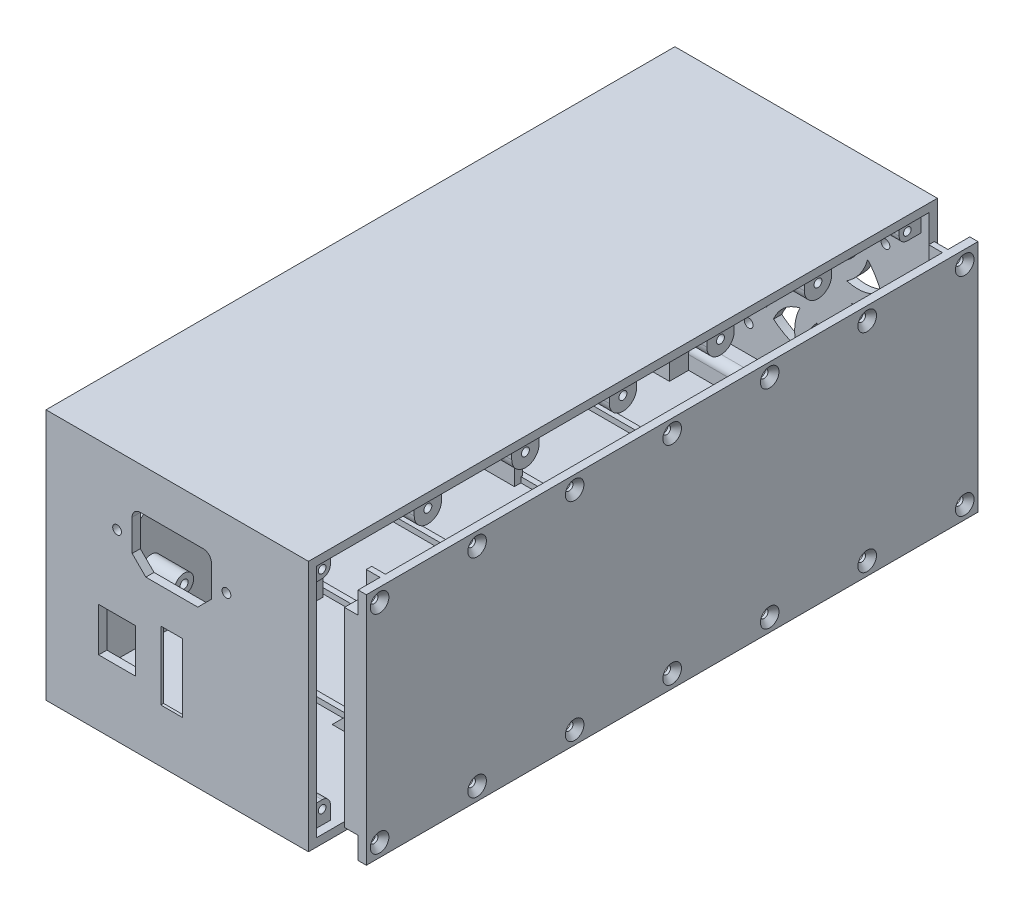
SolidWorks part; units mm, degrees
ref_plane "Front Plane" through (0, 0, 0) normal (0, 0, 1) x (1, 0, 0)
ref_plane "Top Plane" through (0, 0, 0) normal (0, 1, 0) x (1, 0, 0)
ref_plane "Right Plane" through (0, 0, 0) normal (1, 0, 0) x (0, 0, -1)
sketch "Sketch1" plane through (0, 0, 0) normal (1, 0, 0) x (0, 0, -1)
  line L1 (115, 46) -> (-115, 46)
  line L2 (115, 46) -> (115, -46)
  line L3 (115, -46) -> (-115, -46)
  line L4 (-115, 46) -> (-115, -46)
  line L5 (115, 46) -> (-115, -46) construction
  line L6 (115, -46) -> (-115, 46) construction
  point P0 (0, 0)
  dimension "D1" = 92
  dimension "D2" = 230
extrude "Boss-Extrude1" add sketch "Sketch1" along normal blind 3
sketch "Sketch2" plane through (3, 0, 0) normal (1, 0, 0) x (0, 0, -1)
  line L0 (-112, 43) -> (-112, -43)
  line L1 (-112, -43) -> (112, -43)
  line L2 (112, -43) -> (112, 43)
  line L3 (112, 43) -> (-112, 43)
  line L4 (-115, 46) -> (-115, -46)
  line L5 (-115, -46) -> (115, -46)
  line L6 (115, -46) -> (115, 46)
  line L7 (115, 46) -> (-115, 46)
  line L8 (-115, 46) -> (-115, -46)
  line L9 (-115, -46) -> (115, -46)
  line L10 (115, -46) -> (115, 46)
  line L11 (115, 46) -> (-115, 46)
  dimension "D1" = 0
  dimension "D2" = 3
extrude "Boss-Extrude2" add sketch "Sketch2" along normal blind 93
sketch "Sketch3" plane through (0, 0, 0) normal (-1, 0, 0) x (0, 0, 1)
  line L0 (-115, 0) -> (115, 0) construction
  line L1 (-115, -46) -> (-115, 46) construction
  line L2 (115, 46) -> (115, -46) construction
  line L3 (0, 46) -> (0, -46) construction
  line L4 (-115, 46) -> (115, 46) construction
  line L5 (115, -46) -> (-115, -46) construction
  line L6 (26.5, -7.75) -> (18.5, -7.75)
  line L7 (11.5, 7.75) -> (3.5, 7.75)
  line L8 (11.5, 7.75) -> (11.5, -7.75)
  line L9 (11.5, -7.75) -> (3.5, -7.75)
  line L10 (3.5, 7.75) -> (3.5, -7.75)
  line L11 (11.5, 7.75) -> (3.5, -7.75) construction
  line L12 (11.5, -7.75) -> (3.5, 7.75) construction
  line L13 (26.5, 7.75) -> (26.5, -7.75)
  line L14 (26.5, 7.75) -> (18.5, 7.75)
  line L15 (18.5, 7.75) -> (18.5, -7.75)
  line L16 (41.5, -7.75) -> (33.5, -7.75)
  line L17 (41.5, 7.75) -> (41.5, -7.75)
  line L18 (41.5, 7.75) -> (33.5, 7.75)
  line L19 (33.5, 7.75) -> (33.5, -7.75)
  line L20 (56.5, -7.75) -> (48.5, -7.75)
  line L21 (56.5, 7.75) -> (56.5, -7.75)
  line L22 (56.5, 7.75) -> (48.5, 7.75)
  line L23 (48.5, 7.75) -> (48.5, -7.75)
  line L24 (71.5, -7.75) -> (63.5, -7.75)
  line L25 (71.5, 7.75) -> (71.5, -7.75)
  line L26 (71.5, 7.75) -> (63.5, 7.75)
  line L27 (63.5, 7.75) -> (63.5, -7.75)
  line L28 (11.5, -7.75) -> (3.5, -7.75)
  line L29 (11.5, 7.75) -> (11.5, -7.75)
  line L30 (11.5, 7.75) -> (3.5, 7.75)
  line L31 (3.5, 7.75) -> (3.5, -7.75)
  line L32 (26.5, -7.75) -> (18.5, -7.75)
  line L33 (26.5, 7.75) -> (26.5, -7.75)
  line L34 (26.5, 7.75) -> (18.5, 7.75)
  line L35 (18.5, 7.75) -> (18.5, -7.75)
  line L36 (41.5, -7.75) -> (33.5, -7.75)
  line L37 (41.5, 7.75) -> (41.5, -7.75)
  line L38 (41.5, 7.75) -> (33.5, 7.75)
  line L39 (33.5, 7.75) -> (33.5, -7.75)
  line L40 (56.5, -7.75) -> (48.5, -7.75)
  line L41 (56.5, 7.75) -> (56.5, -7.75)
  line L42 (56.5, 7.75) -> (48.5, 7.75)
  line L43 (48.5, 7.75) -> (48.5, -7.75)
  line L44 (-3.5, -7.75) -> (-11.5, -7.75)
  line L45 (-3.5, 7.75) -> (-3.5, -7.75)
  line L46 (-3.5, 7.75) -> (-11.5, 7.75)
  line L47 (-11.5, 7.75) -> (-11.5, -7.75)
  line L48 (11.5, -7.75) -> (3.5, -7.75)
  line L49 (11.5, 7.75) -> (11.5, -7.75)
  line L50 (11.5, 7.75) -> (3.5, 7.75)
  line L51 (3.5, 7.75) -> (3.5, -7.75)
  line L52 (26.5, -7.75) -> (18.5, -7.75)
  line L53 (26.5, 7.75) -> (26.5, -7.75)
  line L54 (26.5, 7.75) -> (18.5, 7.75)
  line L55 (18.5, 7.75) -> (18.5, -7.75)
  line L56 (41.5, -7.75) -> (33.5, -7.75)
  line L57 (41.5, 7.75) -> (41.5, -7.75)
  line L58 (41.5, 7.75) -> (33.5, 7.75)
  line L59 (33.5, 7.75) -> (33.5, -7.75)
  line L60 (-18.5, -7.75) -> (-26.5, -7.75)
  line L61 (-18.5, 7.75) -> (-18.5, -7.75)
  line L62 (-18.5, 7.75) -> (-26.5, 7.75)
  line L63 (-26.5, 7.75) -> (-26.5, -7.75)
  line L64 (-3.5, -7.75) -> (-11.5, -7.75)
  line L65 (-3.5, 7.75) -> (-3.5, -7.75)
  line L66 (-3.5, 7.75) -> (-11.5, 7.75)
  line L67 (-11.5, 7.75) -> (-11.5, -7.75)
  line L68 (11.5, -7.75) -> (3.5, -7.75)
  line L69 (11.5, 7.75) -> (11.5, -7.75)
  line L70 (11.5, 7.75) -> (3.5, 7.75)
  line L71 (3.5, 7.75) -> (3.5, -7.75)
  line L72 (26.5, -7.75) -> (18.5, -7.75)
  line L73 (26.5, 7.75) -> (26.5, -7.75)
  line L74 (26.5, 7.75) -> (18.5, 7.75)
  line L75 (18.5, 7.75) -> (18.5, -7.75)
  line L76 (-33.5, -7.75) -> (-41.5, -7.75)
  line L77 (-33.5, 7.75) -> (-33.5, -7.75)
  line L78 (-33.5, 7.75) -> (-41.5, 7.75)
  line L79 (-41.5, 7.75) -> (-41.5, -7.75)
  line L80 (-18.5, -7.75) -> (-26.5, -7.75)
  line L81 (-18.5, 7.75) -> (-18.5, -7.75)
  line L82 (-18.5, 7.75) -> (-26.5, 7.75)
  line L83 (-26.5, 7.75) -> (-26.5, -7.75)
  line L84 (-3.5, -7.75) -> (-11.5, -7.75)
  line L85 (-3.5, 7.75) -> (-3.5, -7.75)
  line L86 (-3.5, 7.75) -> (-11.5, 7.75)
  line L87 (-11.5, 7.75) -> (-11.5, -7.75)
  line L88 (11.5, -7.75) -> (3.5, -7.75)
  line L89 (11.5, 7.75) -> (11.5, -7.75)
  line L90 (11.5, 7.75) -> (3.5, 7.75)
  line L91 (3.5, 7.75) -> (3.5, -7.75)
  line L92 (-48.5, -7.75) -> (-56.5, -7.75)
  line L93 (-48.5, 7.75) -> (-48.5, -7.75)
  line L94 (-48.5, 7.75) -> (-56.5, 7.75)
  line L95 (-56.5, 7.75) -> (-56.5, -7.75)
  line L96 (-33.5, -7.75) -> (-41.5, -7.75)
  line L97 (-33.5, 7.75) -> (-33.5, -7.75)
  line L98 (-33.5, 7.75) -> (-41.5, 7.75)
  line L99 (-41.5, 7.75) -> (-41.5, -7.75)
  line L100 (-18.5, -7.75) -> (-26.5, -7.75)
  line L101 (-18.5, 7.75) -> (-18.5, -7.75)
  line L102 (-18.5, 7.75) -> (-26.5, 7.75)
  line L103 (-26.5, 7.75) -> (-26.5, -7.75)
  line L104 (-3.5, -7.75) -> (-11.5, -7.75)
  line L105 (-3.5, 7.75) -> (-3.5, -7.75)
  line L106 (-3.5, 7.75) -> (-11.5, 7.75)
  line L107 (-11.5, 7.75) -> (-11.5, -7.75)
  line L108 (-3.5, -7.75) -> (-11.5, -7.75)
  line L109 (-3.5, 7.75) -> (-3.5, -7.75)
  line L110 (-3.5, 7.75) -> (-11.5, 7.75)
  line L111 (-11.5, 7.75) -> (-11.5, -7.75)
  line L112 (-18.5, -7.75) -> (-26.5, -7.75)
  line L113 (-18.5, 7.75) -> (-18.5, -7.75)
  line L114 (-18.5, 7.75) -> (-26.5, 7.75)
  line L115 (-26.5, 7.75) -> (-26.5, -7.75)
  line L116 (-33.5, -7.75) -> (-41.5, -7.75)
  line L117 (-33.5, 7.75) -> (-33.5, -7.75)
  line L118 (-33.5, 7.75) -> (-41.5, 7.75)
  line L119 (-41.5, 7.75) -> (-41.5, -7.75)
  line L120 (-48.5, -7.75) -> (-56.5, -7.75)
  line L121 (-48.5, 7.75) -> (-48.5, -7.75)
  line L122 (-48.5, 7.75) -> (-56.5, 7.75)
  line L123 (-56.5, 7.75) -> (-56.5, -7.75)
  line L124 (-63.5, -7.75) -> (-71.5, -7.75)
  line L125 (-63.5, 7.75) -> (-63.5, -7.75)
  line L126 (-63.5, 7.75) -> (-71.5, 7.75)
  line L127 (-71.5, 7.75) -> (-71.5, -7.75)
  circle A0 centre (84.6037, 0) radius 1
  point P12 (7.5, 0)
  dimension "D6" = 2
  dimension "D1" = 7.5
  dimension "D2" = 15.5
  dimension "D3" = 8
  dimension "D4" = 5
  dimension "D5" = 6
extrude "Cut-Extrude1" cut sketch "Sketch3" against normal up to surface (3 mm away) contours L126 L127 L124 L125 | L94 L95 L92 L93 | L78 L79 L76 L77 | L62 L63 L60 L61 | L46 L47 L44 L45 | L7 L10 L9 L8 | L14 L15 L6 L13 | L18 L19 L16 L17 | L22 L23 L20 L21 | L26 L27 L24 L25 | A0 region at (0, 0, 22.5) region at (0, 0, 7.5) region at (0, 0, 37.5) region at (0, 0, 52.5) region at (0, 0, 67.5) region at (0, 0, -7.5) region at (0, 0, -22.5) region at (0, 0, -37.5) region at (0, 0, -52.5) region at (0, 0, -67.5) region at (0, 0, 84.6037) up to face at (3, 0, 0)
sketch "Sketch4" plane through (96, 0, 0) normal (1, 0, 0) x (0, 0, -1)
  line L0 (0, 43) -> (0, -43) construction
  line L1 (112, 43) -> (-112, 43) construction
  line L2 (-112, -43) -> (112, -43) construction
  line L3 (-112, 43) -> (-112, -43) construction
  line L4 (-104, 38) -> (-104, 43)
  line L5 (-104, 43) -> (-112, 43)
  line L6 (-112, 43) -> (-112, 35)
  line L7 (-112, 35) -> (-107, 35)
  line L8 (0, 0) -> (-112, 0) construction
  line L9 (-107, -35) -> (-112, -35)
  line L10 (-112, 43) -> (-112, -43) construction
  line L11 (-112, -35) -> (-112, -43)
  line L12 (-104, -38) -> (-104, -43)
  line L13 (-104, -43) -> (-112, -43)
  line L14 (104, -43) -> (112, -43)
  line L15 (112, -35) -> (112, -43)
  line L16 (107, -35) -> (112, -35)
  line L17 (112, 35) -> (107, 35)
  line L18 (112, 43) -> (112, 35)
  line L19 (104, 43) -> (112, 43)
  line L20 (104, 38) -> (104, 43)
  line L21 (104, -38) -> (104, -43)
  circle A0 centre (-107, 38) radius 1.4
  circle A1 centre (-107, -38) radius 1.4
  arc A2 (-104, 38) -> (-107, 35) centre (-107, 38) cw
  arc A3 (-107, -35) -> (-104, -38) centre (-107, -38) cw
  arc A4 (107, -35) -> (104, -38) centre (107, -38) ccw
  circle A5 centre (107, -38) radius 1.4
  arc A6 (104, 38) -> (107, 35) centre (107, 38) ccw
  circle A7 centre (107, 38) radius 1.4
  dimension "D5" = 2.8
  dimension "D6" = 3
  dimension "D1" = 5
  dimension "D2" = 5
  dimension "D3" = 5
  dimension "D4" = 5
extrude "Boss-Extrude3" add sketch "Sketch4" against normal up to surface (93 mm away) from offset 3 up to face at (3, 0, -67.5) offset against normal yes
sketch "Sketch5" plane through (93, 0, 0) normal (1, 0, 0) x (0, 0, -1)
  circle A0 centre (-107, -38) radius 1.4 construction
  circle A1 centre (107, -38) radius 1.4 construction
  circle A2 centre (107, 38) radius 1.4 construction
  circle A3 centre (-107, 38) radius 1.4 construction
  circle A4 centre (-107, -38) radius 1.4
  circle A5 centre (107, -38) radius 1.4
  circle A6 centre (107, 38) radius 1.4
  circle A7 centre (-107, 38) radius 1.4
extrude "Boss-Extrude4" add sketch "Sketch5" against normal up to surface (90 mm away) from offset 20 up to face at (3, 0, -67.5) offset against normal yes
sketch "Sketch6" plane through (0, 0, 115) normal (0, 0, 1) x (1, 0, 0)
  line L0 (46, 46) -> (46, -46) construction
  line L1 (96, 46) -> (0, 46) construction
  line L2 (96, -46) -> (0, -46) construction
  line L3 (93, 43) -> (93, 38) construction
  line L4 (79.2275, 21) -> (12.7725, 21) construction
  line L5 (36.5, 11.25) -> (31.5, 16.25)
  line L6 (57.5, 30.75) -> (34.5, 30.75)
  line L7 (60.5, 27.75) -> (60.5, 16.25)
  line L8 (55.5, 11.25) -> (36.5, 11.25)
  line L9 (31.5, 27.75) -> (31.5, 16.25)
  line L10 (60.5, 30.75) -> (31.5, 11.25) construction
  line L11 (60.5, 11.25) -> (31.5, 30.75) construction
  line L12 (60.5, 16.25) -> (55.5, 11.25)
  line L14 (50, -1.5) -> (42, -1.5)
  line L15 (50, -1.5) -> (50, -26.5)
  line L16 (50, -26.5) -> (42, -26.5)
  line L17 (42, -1.5) -> (42, -26.5)
  line L18 (50, -1.5) -> (42, -26.5) construction
  line L19 (50, -26.5) -> (42, -1.5) construction
  line L20 (32.75, -6) -> (19.25, -6)
  line L21 (32.75, -6) -> (32.75, -22)
  line L22 (32.75, -22) -> (19.25, -22)
  line L23 (19.25, -6) -> (19.25, -22)
  line L24 (32.75, -6) -> (19.25, -22) construction
  line L25 (32.75, -22) -> (19.25, -6) construction
  circle A2 centre (26, 21) radius 1.6
  circle A3 centre (66, 21) radius 1.6
  arc A4 (57.5, 30.75) -> (60.5, 27.75) centre (57.5, 27.75) cw
  arc A5 (34.5, 30.75) -> (31.5, 27.75) centre (34.5, 27.75) ccw
  point P11 (46, 21)
  point P15 (46, 21)
  point P30 (46, -14)
  point P35 (26, -14)
  dimension "D2" = 3.2
  dimension "D7" = 3
  dimension "D1" = 47
  dimension "D3" = 20
  dimension "D4" = 20
  dimension "D5" = 29
  dimension "D6" = 19.5
  dimension "D8" = 25
  dimension "D9" = 8
  dimension "D10" = 25
  dimension "D13" = 32
  dimension "D14" = 20
  dimension "D15" = 13.5
  dimension "D16" = 16
extrude "Cut-Extrude2" cut sketch "Sketch6" against normal up to surface (3 mm away) up to face at (71.25, 0, 112)
sketch "Sketch7" plane through (0, 0, 112) normal (0, 0, -1) x (-1, 0, 0)
  line L0 (-39.5, 6) -> (-39.5, -32.5)
  line L1 (-39.5, -32.5) -> (-52, -32.5)
  line L2 (-52, -32.5) -> (-52, 6)
  line L3 (-52, 6) -> (-39.5, 6)
  line L4 (-50, -1.5) -> (-42, -1.5) construction
  line L5 (-50, -26.5) -> (-50, -1.5) construction
  dimension "D1" = 7.5
  dimension "D2" = 2
  dimension "D3" = 38.5
  dimension "D4" = 12.5
extrude "Cut-Extrude3" cut sketch "Sketch7" against normal blind 2
chamfer "Chamfer1" distance 2 angle 45 1 edges at (52, -13.25, 112)
sketch "Sketch8" plane through (3, 0, 0) normal (1, 0, 0) x (0, 0, -1)
  line L0 (-71.5, 0) -> (91.1958, 0) construction
  line L1 (-71.5, -7.75) -> (-71.5, 7.75) construction
  line L2 (-79.5, 43) -> (-79.5, -43) construction
  line L3 (112, 43) -> (-112, 43) construction
  line L4 (-104, -43) -> (104, -43) construction
  circle A0 centre (-79.5, 19.5) radius 1.5
  circle A1 centre (-79.5, -19.5) radius 1.5
  circle A2 centre (-79.5, 19.5) radius 3.5
  circle A3 centre (-79.5, -19.5) radius 3.5
  circle A4 centre (72, -19.5) radius 1.5
  circle A5 centre (72, -19.5) radius 3.5
  circle A6 centre (72, 19.5) radius 3.5
  circle A7 centre (72, 19.5) radius 1.5
  dimension "D1" = 3
  dimension "D2" = 7
  dimension "D3" = 8
  dimension "D5" = 19.5
  dimension "D6" = 19.5
  dimension "D7" = 19.5
  dimension "D8" = 19.5
  dimension "D9" = 151.5
extrude "Boss-Extrude5" add sketch "Sketch8" along normal blind 12
sketch "Sketch9" plane through (3, 0, 0) normal (1, 0, 0) x (0, 0, -1)
  circle A0 centre (-84.6037, 0) radius 3
extrude "Cut-Extrude4" cut sketch "Sketch9" against normal blind 2.2
ref_plane "Plane1" through (106, 0, 0) normal (1, 0, 0) x (0, 0, -1)
sketch "Sketch10" plane through (106, 0, 0) normal (1, 0, 0) x (0, 0, -1)
  line L112 (107, -32.85) -> (109.85, -32.85)
  line L113 (109.85, -32.85) -> (109.85, 32.85)
  line L114 (109.85, 32.85) -> (107, 32.85)
  line L115 (101.85, 38) -> (101.85, 40.85)
  line L116 (101.85, 40.85) -> (-101.85, 40.85)
  line L117 (-101.85, 40.85) -> (-101.85, 38)
  line L118 (-107, 32.85) -> (-109.85, 32.85)
  line L119 (-109.85, 32.85) -> (-109.85, -32.85)
  line L120 (-109.85, -32.85) -> (-107, -32.85)
  line L121 (-101.85, -38) -> (-101.85, -40.85)
  line L122 (-101.85, -40.85) -> (101.85, -40.85)
  line L123 (101.85, -40.85) -> (101.85, -38)
  line L124 (107, -34.85) -> (111.85, -34.85)
  line L125 (103.85, -42.85) -> (103.85, -38)
  line L126 (-103.85, -42.85) -> (103.85, -42.85)
  line L127 (-103.85, -38) -> (-103.85, -42.85)
  line L128 (-111.85, -34.85) -> (-107, -34.85)
  line L129 (-111.85, 34.85) -> (-111.85, -34.85)
  line L130 (-107, 34.85) -> (-111.85, 34.85)
  line L131 (-103.85, 42.85) -> (-103.85, 38)
  line L132 (103.85, 42.85) -> (-103.85, 42.85)
  line L133 (103.85, 38) -> (103.85, 42.85)
  line L134 (111.85, 34.85) -> (107, 34.85)
  line L135 (111.85, -34.85) -> (111.85, 34.85)
  line L136 (107, -34.85) -> (111.85, -34.85)
  line L137 (103.85, -42.85) -> (103.85, -38)
  line L138 (-103.85, -42.85) -> (103.85, -42.85)
  line L139 (-103.85, -38) -> (-103.85, -42.85)
  line L140 (-111.85, -34.85) -> (-107, -34.85)
  line L141 (-111.85, 34.85) -> (-111.85, -34.85)
  line L142 (-107, 34.85) -> (-111.85, 34.85)
  line L143 (-103.85, 42.85) -> (-103.85, 38)
  line L144 (103.85, 42.85) -> (-103.85, 42.85)
  line L145 (103.85, 38) -> (103.85, 42.85)
  line L146 (111.85, 34.85) -> (107, 34.85)
  line L147 (111.85, -34.85) -> (111.85, 34.85)
  arc A36 (107, -34.85) -> (103.85, -38) centre (107, -38) ccw
  arc A37 (-103.85, -38) -> (-107, -34.85) centre (-107, -38) ccw
  arc A38 (-107, 34.85) -> (-103.85, 38) centre (-107, 38) ccw
  arc A39 (103.85, 38) -> (107, 34.85) centre (107, 38) ccw
  arc A40 (107, -34.85) -> (103.85, -38) centre (107, -38) ccw
  arc A41 (-103.85, -38) -> (-107, -34.85) centre (-107, -38) ccw
  arc A42 (-107, 34.85) -> (-103.85, 38) centre (-107, 38) ccw
  arc A43 (103.85, 38) -> (107, 34.85) centre (107, 38) ccw
  arc A48 (101.85, 38) -> (107, 32.85) centre (107, 38) ccw
  arc A49 (-107, 32.85) -> (-101.85, 38) centre (-107, 38) ccw
  arc A50 (-101.85, -38) -> (-107, -32.85) centre (-107, -38) ccw
  arc A51 (107, -32.85) -> (101.85, -38) centre (107, -38) ccw
  dimension "D1" = 0.15
  dimension "D2" = 2
extrude "Boss-Extrude6" add sketch "Sketch10" along normal blind 5 separate body
sketch "Sketch11" plane through (111, 0, 0) normal (1, 0, 0) x (0, 0, -1)
  line L0 (111.85, -34.85) -> (111.85, 34.85) construction
  line L1 (-103.85, -42.85) -> (103.85, -42.85) construction
  line L2 (-111.85, 34.85) -> (-111.85, -34.85) construction
  line L3 (103.85, 42.85) -> (-103.85, 42.85) construction
  line L4 (111.85, -34.85) -> (111.85, 34.85)
  line L5 (-103.85, -42.85) -> (103.85, -42.85)
  line L6 (-111.85, 34.85) -> (-111.85, -34.85)
  line L7 (103.85, 42.85) -> (-103.85, 42.85)
  line L8 (103.85, 42.85) -> (111.85, 42.85)
  line L9 (111.85, 42.85) -> (111.85, 34.85)
  line L10 (111.85, -34.85) -> (111.85, -42.85)
  line L11 (111.85, -42.85) -> (103.85, -42.85)
  line L12 (-111.85, -34.85) -> (-111.85, -42.85)
  line L13 (-111.85, -42.85) -> (-103.85, -42.85)
  line L14 (-103.85, 42.85) -> (-111.85, 42.85)
  line L15 (-111.85, 42.85) -> (-111.85, 34.85)
  circle A0 centre (-107, -38) radius 1.4 construction
  circle A1 centre (107, -38) radius 1.4 construction
  circle A2 centre (107, 38) radius 1.4 construction
  circle A3 centre (-107, 38) radius 1.4 construction
  circle A4 centre (-107, -38) radius 1.4
  circle A5 centre (107, -38) radius 1.4
  circle A6 centre (107, 38) radius 1.4
  circle A7 centre (-107, 38) radius 1.4
extrude "Boss-Extrude7" add sketch "Sketch11" along normal blind 3
sketch "Sketch12" plane through (114, 0, 0) normal (1, 0, 0) x (0, 0, -1)
  line L0 (-112, 0) -> (111.85, 0) construction
  line L1 (89, 29.25) -> (-89, 29.25) construction
  line L2 (89, 29.25) -> (89, -29.25) construction
  line L3 (89, -29.25) -> (-89, -29.25) construction
  line L4 (-89, 29.25) -> (-89, -29.25) construction
  line L5 (89, 29.25) -> (-89, -29.25) construction
  line L6 (89, -29.25) -> (-89, 29.25) construction
  line L7 (-112, 43) -> (-112, -43) construction
  line L8 (111.85, -42.85) -> (111.85, 42.85) construction
  circle A0 centre (-89, 29.25) radius 1.8
  circle A1 centre (-89, -29.25) radius 1.8
  circle A2 centre (89, -29.25) radius 1.8
  circle A3 centre (89, 29.25) radius 1.8
  circle A4 centre (-47.3819, 9) radius 1.8
  circle A5 centre (26.6181, 9) radius 1.8
  circle A6 centre (-4.3819, 9) radius 1.8
  circle A7 centre (-4.3819, -9) radius 1.8
  point P0 (0, 0)
  dimension "D3" = 3.6
  dimension "D10" = 3.6
  dimension "D1" = 58.5
  dimension "D2" = 178
  dimension "D4" = 9
  dimension "D5" = 9
  dimension "D6" = 74
  dimension "D7" = 31
  dimension "D8" = 9
  dimension "D9" = 9
sketch "Sketch13" plane through (96, 0, 0) normal (1, 0, 0) x (0, 0, -1)
  line L12 (104, 38) -> (104, 43)
  line L13 (104, 43) -> (-104, 43)
  line L14 (-104, 43) -> (-104, 38)
  line L15 (-107, 35) -> (-112, 35)
  line L16 (-112, 35) -> (-112, -35)
  line L17 (-112, -35) -> (-107, -35)
  line L18 (-104, -38) -> (-104, -43)
  line L19 (-104, -43) -> (104, -43)
  line L20 (104, -43) -> (104, -38)
  line L21 (107, -35) -> (112, -35)
  line L22 (112, -35) -> (112, 35)
  line L23 (112, 35) -> (107, 35)
  line L24 (104, 38) -> (104, 43)
  line L25 (104, 43) -> (-104, 43)
  line L26 (-104, 43) -> (-104, 38)
  line L27 (-107, 35) -> (-112, 35)
  line L28 (-112, 35) -> (-112, -35)
  line L29 (-112, -35) -> (-107, -35)
  line L30 (-104, -38) -> (-104, -43)
  line L31 (-104, -43) -> (104, -43)
  line L32 (104, -43) -> (104, -38)
  line L33 (107, -35) -> (112, -35)
  line L34 (112, -35) -> (112, 35)
  line L35 (112, 35) -> (107, 35)
  arc A4 (104, 38) -> (107, 35) centre (107, 38) ccw
  arc A5 (-107, 35) -> (-104, 38) centre (-107, 38) ccw
  arc A6 (-104, -38) -> (-107, -35) centre (-107, -38) ccw
  arc A7 (107, -35) -> (104, -38) centre (107, -38) ccw
  arc A8 (104, 38) -> (107, 35) centre (107, 38) ccw
  arc A9 (-107, 35) -> (-104, 38) centre (-107, 38) ccw
  arc A10 (-104, -38) -> (-107, -35) centre (-107, -38) ccw
  arc A11 (107, -35) -> (104, -38) centre (107, -38) ccw
  dimension "D1" = 0
sketch "Sketch14" plane through (93, 0, 0) normal (1, 0, 0) x (0, 0, -1)
  line L0 (-68.334, -43) -> (-68.334, -41)
  line L2 (-104, -43) -> (-104, -38) construction
  line L3 (-68.334, 43) -> (-68.334, 41)
  line L5 (-104, 38) -> (-104, 43) construction
  dimension "D1" = 35.666
  dimension "D2" = 35.666
extrude "Extrude-Thin2" add sketch "Sketch14" against normal up to surface (90 mm away) from offset 3 thin up to face at (3, 0, 81.6037) offset against normal yes thin type mid plane wall 2
pattern_linear "LPattern1" count 5 spacing 35.666 along (0, 0, -1) of "Extrude-Thin2"
sketch "Sketch15" plane through (3, 40, 0) normal (1, 0, 0) x (0, 1, 0)
  line L0 (-40, 112) -> (-40, -112.6115) construction
  line L2 (-5, 112) -> (-75, 112) construction
  line L3 (-13.5, 36.1943) -> (-66.5, 36.1943) construction
  line L4 (-13.5, 36.1943) -> (-13.5, -36.8057) construction
  line L5 (-13.5, -36.8057) -> (-66.5, -36.8057) construction
  line L6 (-66.5, 36.1943) -> (-66.5, -36.8057) construction
  line L7 (-13.5, 36.1943) -> (-66.5, -36.8057) construction
  line L8 (-13.5, -36.8057) -> (-66.5, 36.1943) construction
  circle A0 centre (-13.5, 36.1943) radius 1.25
  circle A1 centre (-66.5, 36.1943) radius 1.25
  circle A2 centre (-66.5, -36.8057) radius 1.25
  circle A4 centre (-66.5, 36.1943) radius 2.5
  circle A5 centre (-13.5, 36.1943) radius 2.5
  circle A7 centre (-66.5, -36.8057) radius 2.5
  circle A8 centre (-13.5, -36.8057) radius 1.25
  circle A9 centre (-13.5, -36.8057) radius 2.5
  point P4 (-40, -0.3057)
  point P20 (-40, 112)
  dimension "D3" = 2.5
  dimension "D4" = 5
  dimension "D1" = 53
  dimension "D2" = 73
extrude "Boss-Extrude9" add sketch "Sketch15" along normal blind 20
sketch "Sketch16" plane through (0, 0, -112) normal (0, 0, 1) x (1, 0, 0)
  line L0 (3, 0) -> (96, 0) construction
  line L1 (3, -35) -> (3, 35) construction
  line L3 (55, 0) -> (67.5, 0) construction
  line L4 (80, 25) -> (30, 25) construction
  line L5 (80, 25) -> (80, -25) construction
  line L6 (80, -25) -> (30, -25) construction
  line L7 (30, 25) -> (30, -25) construction
  line L8 (80, 25) -> (30, -25) construction
  line L9 (80, -25) -> (30, 25) construction
  line L10 (55, 0) -> (65.8253, -6.25) construction
  line L11 (96, -35) -> (96, 35) construction
  circle A0 centre (30, 25) radius 1.6
  circle A1 centre (80, 25) radius 1.6
  circle A2 centre (80, -25) radius 1.6
  circle A3 centre (30, -25) radius 1.6
  circle A4 centre (55, 0) radius 12.5 construction
  arc A5 (79.4256, 5.3285) -> (79.6515, -4.1595) centre (55, 0) cw
  arc A6 (78.8174, -7.5982) -> (74.2691, -15.928) centre (55, 0) cw
  arc A7 (71.8274, -18.4889) -> (63.7236, -23.4286) centre (55, 0) cw
  arc A8 (60.3285, -24.4256) -> (50.8405, -24.6515) centre (55, 0) cw
  arc A9 (47.4018, -23.8174) -> (39.072, -19.2691) centre (55, 0) cw
  arc A10 (36.5111, -16.8274) -> (31.5714, -8.7236) centre (55, 0) cw
  arc A11 (30.5744, -5.3285) -> (30.3485, 4.1595) centre (55, 0) cw
  arc A12 (31.1826, 7.5982) -> (35.7309, 15.928) centre (55, 0) cw
  arc A13 (38.1726, 18.4889) -> (46.2764, 23.4286) centre (55, 0) cw
  arc A14 (49.6715, 24.4256) -> (59.1595, 24.6515) centre (55, 0) cw
  arc A15 (62.5982, 23.8174) -> (70.928, 19.2691) centre (55, 0) cw
  arc A16 (73.4889, 16.8274) -> (78.4286, 8.7236) centre (55, 0) cw
  spline S0 degree 2 poles (79.4256, 5.3285) (74.5238, 0.5174) (67.5, 0) knots 0 0 0 1 1 1
  spline S1 degree 2 poles (67.5, 0) (72.6575, -5.0815) (79.6515, -4.1595) knots 0 0 0 1 1 1
  spline S2 degree 2 poles (78.8174, -7.5982) (72.1668, -9.3138) (65.8253, -6.25) knots 0 0 0 1 1 1
  spline S3 degree 2 poles (65.8253, -6.25) (67.7511, -13.2294) (74.2691, -15.928) knots 0 0 0 1 1 1
  spline S4 degree 2 poles (71.8274, -18.4889) (65.21, -16.6494) (61.25, -10.8253) knots 0 0 0 1 1 1
  spline S5 degree 2 poles (61.25, -10.8253) (59.428, -17.8326) (63.7236, -23.4286) knots 0 0 0 1 1 1
  spline S6 degree 2 poles (60.3285, -24.4256) (55.5174, -19.5238) (55, -12.5) knots 0 0 0 1 1 1
  spline S7 degree 2 poles (55, -12.5) (49.9185, -17.6575) (50.8405, -24.6515) knots 0 0 0 1 1 1
  spline S8 degree 2 poles (47.4018, -23.8174) (45.6862, -17.1668) (48.75, -10.8253) knots 0 0 0 1 1 1
  spline S9 degree 2 poles (48.75, -10.8253) (41.7706, -12.7511) (39.072, -19.2691) knots 0 0 0 1 1 1
  spline S10 degree 2 poles (36.5111, -16.8274) (38.3506, -10.21) (44.1747, -6.25) knots 0 0 0 1 1 1
  spline S11 degree 2 poles (44.1747, -6.25) (37.1674, -4.428) (31.5714, -8.7236) knots 0 0 0 1 1 1
  spline S12 degree 2 poles (30.5744, -5.3285) (35.4762, -0.5174) (42.5, 0) knots 0 0 0 1 1 1
  spline S13 degree 2 poles (42.5, 0) (37.3425, 5.0815) (30.3485, 4.1595) knots 0 0 0 1 1 1
  spline S14 degree 2 poles (31.1826, 7.5982) (37.8332, 9.3138) (44.1747, 6.25) knots 0 0 0 1 1 1
  spline S15 degree 2 poles (44.1747, 6.25) (42.2489, 13.2294) (35.7309, 15.928) knots 0 0 0 1 1 1
  spline S16 degree 2 poles (38.1726, 18.4889) (44.79, 16.6494) (48.75, 10.8253) knots 0 0 0 1 1 1
  spline S17 degree 2 poles (48.75, 10.8253) (50.572, 17.8326) (46.2764, 23.4286) knots 0 0 0 1 1 1
  spline S18 degree 2 poles (49.6715, 24.4256) (54.4826, 19.5238) (55, 12.5) knots 0 0 0 1 1 1
  spline S19 degree 2 poles (55, 12.5) (60.0815, 17.6575) (59.1595, 24.6515) knots 0 0 0 1 1 1
  spline S20 degree 2 poles (62.5982, 23.8174) (64.3138, 17.1668) (61.25, 10.8253) knots 0 0 0 1 1 1
  spline S21 degree 2 poles (61.25, 10.8253) (68.2294, 12.7511) (70.928, 19.2691) knots 0 0 0 1 1 1
  spline S22 degree 2 poles (73.4889, 16.8274) (71.6494, 10.21) (65.8253, 6.25) knots 0 0 0 1 1 1
  spline S23 degree 2 poles (65.8253, 6.25) (72.8326, 4.428) (78.4286, 8.7236) knots 0 0 0 1 1 1
  point P6 (55, 0)
  point P83 (96, 0)
  dimension "D4" = 3.2
  dimension "D5" = 25
  dimension "D6" = 12
  dimension "D1" = 50
  dimension "D2" = 50
  dimension "D7" = 30
extrude "Cut-Extrude6" cut sketch "Sketch16" against normal up to surface (3 mm away) up to face at (48, 0, -115)
sketch "Sketch17" plane through (111, 0, 0) normal (-1, 0, 0) x (0, 0, 1)
  line L0 (-109.85, -0.85) -> (109.85, -0.85) construction
  line L1 (-109.85, -32.85) -> (-109.85, 32.85) construction
  line L2 (109.85, 32.85) -> (109.85, -32.85) construction
  line L3 (101.85, -40.85) -> (-101.85, -40.85) construction
  line L4 (-8.5, 20.1) -> (-91.2, 20.1) construction
  line L5 (-8.5, 20.1) -> (-8.5, -21.8) construction
  line L6 (-8.5, -21.8) -> (-91.2, -21.8) construction
  line L7 (-91.2, 20.1) -> (-91.2, -21.8) construction
  line L8 (-8.5, 20.1) -> (-91.2, -21.8) construction
  line L9 (-8.5, -21.8) -> (-91.2, 20.1) construction
  line L10 (79.15, 12.15) -> (21.15, 12.15) construction
  line L11 (79.15, 12.15) -> (79.15, -13.85) construction
  line L12 (79.15, -13.85) -> (21.15, -13.85) construction
  line L13 (21.15, 12.15) -> (21.15, -13.85) construction
  line L14 (79.15, 12.15) -> (21.15, -13.85) construction
  line L15 (79.15, -13.85) -> (21.15, 12.15) construction
  line L16 (-109.85, -32.85) -> (-109.85, 32.85) construction
  circle A0 centre (-91.2, 20.1) radius 1.4
  circle A1 centre (-91.2, -21.8) radius 1.4
  circle A2 centre (-8.5, -21.8) radius 1.4
  circle A3 centre (-8.5, 20.1) radius 1.4
  circle A4 centre (79.15, 12.15) radius 1.4
  circle A5 centre (21.15, 12.15) radius 1.4
  circle A6 centre (21.15, -13.85) radius 1.4
  circle A7 centre (79.15, -13.85) radius 1.4
  circle A8 centre (-91.2, 20.1) radius 3.25
  circle A9 centre (-8.5, 20.1) radius 3.25
  circle A10 centre (-8.5, -21.8) radius 3.25
  circle A11 centre (-91.2, -21.8) radius 3.25
  circle A12 centre (21.15, -13.85) radius 3.25
  circle A13 centre (21.15, 12.15) radius 3.25
  circle A14 centre (79.15, 12.15) radius 3.25
  circle A15 centre (79.15, -13.85) radius 3.25
  point P6 (-49.85, -0.85)
  point P11 (50.15, -0.85)
  dimension "D8" = 2.8
  dimension "D9" = 6.5
  dimension "D1" = 82.7
  dimension "D2" = 41.9
  dimension "D3" = 40
  dimension "D4" = 60
  dimension "D5" = 58
  dimension "D6" = 26
  dimension "D7" = 100
extrude "Boss-Extrude10" add sketch "Sketch17" along normal blind 5
sketch "Sketch18" plane through (93, 0, 0) normal (1, 0, 0) x (0, 0, -1)
  line L0 (74.33, -41) -> (74.33, -35.3123) construction
  line L1 (73.33, -41) -> (75.33, -41) construction
  line L2 (-112, -43) -> (112, -43) construction
  line L3 (69.33, -38) -> (69.33, -43)
  line L5 (69.33, -43) -> (79.33, -43)
  line L6 (79.33, -43) -> (79.33, -38)
  circle A0 centre (74.33, -38) radius 1.45
  arc A1 (69.33, -38) -> (79.33, -38) centre (74.33, -38) cw
  dimension "D1" = 2.9
  dimension "D3" = 5
  dimension "D2" = 5
extrude "Boss-Extrude11" add sketch "Sketch18" against normal blind 20
chamfer "Chamfer3" distance 10 angle 45 1 edges at (73, -43, -71.33)
ref_plane "Plane2" through (0, 0, 0) normal (0, -1, 0) x (-1, 0, 0)
mirror "Mirror4" about plane through (0, 0, 0) normal (0, -1, 0) of "Boss-Extrude11"
chamfer "Chamfer4" distance 10 angle 45 1 edges at (73, 43, -71.33)
pattern_linear "LPattern4" count 5 spacing 35.666 along (0, 0, 1) of "Boss-Extrude11", "Chamfer3", "Mirror4", "Chamfer4"
sketch "Sketch21" plane through (106, 0, 0) normal (-1, 0, 0) x (0, 0, 1)
  line L0 (-101.85, -44.15) -> (-101.85, -36.4687)
  line L1 (-101.85, 40.85) -> (101.8627, 40.85)
  line L2 (-101.85, 40.85) -> (-101.85, 48.5313)
  line L3 (-101.85, 48.5313) -> (101.8627, 48.5313)
  line L4 (101.8627, 40.85) -> (101.8627, 48.5313)
  line L5 (-101.85, -44.15) -> (101.8627, -44.15)
  line L6 (101.8627, -44.15) -> (101.8627, -36.4687)
  line L7 (-101.85, -36.4687) -> (101.8627, -36.4687)
  dimension "D1" = 2
extrude "Cut-Extrude7" cut sketch "Sketch21" against normal up to surface (5 mm away) up to face at (111, -13.85, 82.4)
sketch "Sketch22" plane through (114, 0, 0) normal (1, 0, 0) x (0, 0, -1)
  line L0 (-107, 38) -> (-71.334, 38) construction
  line L1 (-111.85, 0) -> (111.85, 0) construction
  line L2 (-111.85, 42.85) -> (-111.85, -42.85) construction
  line L3 (111.85, -42.85) -> (111.85, 42.85) construction
  circle A0 centre (-71.334, 38) radius 1.4
  circle A1 centre (-107, 38) radius 1.4 construction
  circle A2 centre (-35.668, 38) radius 1.4
  circle A3 centre (-0.002, 38) radius 1.4
  circle A4 centre (35.664, 38) radius 1.4
  circle A5 centre (71.33, 38) radius 1.4
  circle A6 centre (71.33, -38) radius 1.4
  circle A7 centre (35.664, -38) radius 1.4
  circle A8 centre (-0.002, -38) radius 1.4
  circle A9 centre (-35.668, -38) radius 1.4
  circle A10 centre (-71.334, -38) radius 1.4
  dimension "D2" = 35.666
  dimension "D3" = 35.666
  dimension "D1" = 5
extrude "Cut-Extrude8" cut sketch "Sketch22" against normal up to surface (3 mm away) up to face at (111, 4.5559, 11.3264)
chamfer "Chamfer5" distance 2 angle 45 14 edges at (114, -38, 105.6) (114, -38, 72.734) (114, -38, 37.068) (114, -38, 1.402) (114, -38, -34.264) (114, -38, -69.93) (114, -38, -108.4) (114, 38, -37.064) (114, 38, -1.398) (114, 38, 34.268) (114, 38, 105.6) (114, 38, 69.934) (114, 38, -108.4) (114, 38, -72.73)
sketch "Sketch23" plane through (0, 0, -112) normal (0, 0, 1) x (1, 0, 0)
  line L0 (3, 0) -> (96, 0) construction
  line L1 (3, -35) -> (3, 35) construction
  line L2 (96, -43) -> (96, 43) construction
  line L3 (3, 30.1015) -> (3, 43)
  line L4 (3, 43) -> (93, 43) construction
  line L5 (3, -30.1015) -> (3, 30.1015)
  line L6 (3, 43) -> (16, 43)
  line L11 (3, -43) -> (16, -43)
  line L12 (3, -30.1015) -> (3, -43)
  line L13 (16, -43) -> (16, 43)
  circle A0 centre (8, 35.5) radius 1.6
  circle A1 centre (8, -35.5) radius 1.6
  dimension "D1" = 3.2
  dimension "D2" = 5
  dimension "D3" = 71
  dimension "D4" = 13
extrude "Boss-Extrude12" add sketch "Sketch23" along normal blind 15
sketch "Sketch24" plane through (0, 0, 0) normal (-1, 0, 0) x (0, 0, 1)
  line L0 (-115, 0) -> (-89.7581, 0) construction
  line L1 (-115, -46) -> (-115, 46) construction
  line L3 (-101.8, 40.1) -> (-112, 40.1)
  line L4 (-101.8, 40.1) -> (-101.8, -40.1)
  line L5 (-101.8, -40.1) -> (-112, -40.1)
  line L6 (-112, 40.1) -> (-112, -40.1)
  line L7 (-101.8, 40.1) -> (-112, -40.1) construction
  line L8 (-101.8, -40.1) -> (-112, 40.1) construction
  point P5 (-106.9, 0)
  dimension "D1" = 3
  dimension "D2" = 10.2
  dimension "D3" = 80.2
extrude "Cut-Extrude9" cut sketch "Sketch24" against normal blind 13
sketch "Sketch25" plane through (0, 0, -115) normal (0, 0, -1) x (-1, 0, 0)
  circle A0 centre (-8, 35.5) radius 1.6
  circle A1 centre (-8, -35.5) radius 1.6
  dimension "D1" = 3.2
extrude "Cut-Extrude10" cut sketch "Sketch25" against normal up to surface (3 mm away) up to face at (46.3903, -18.8616, -112)
sketch "Sketch26" plane through (23, 0, 0) normal (1, 0, 0) x (0, 0, -1)
  line L1 (53.3288, 25) -> (-53.3288, 25)
  line L2 (53.3288, 25) -> (53.3288, -25)
  line L3 (53.3288, -25) -> (-53.3288, -25)
  line L4 (-53.3288, 25) -> (-53.3288, -25)
  line L5 (53.3288, 25) -> (-53.3288, -25) construction
  line L6 (53.3288, -25) -> (-53.3288, 25) construction
  point P0 (0, 0)
  dimension "D1" = 50
extrude "Cut-Extrude11" cut sketch "Sketch26" against normal up to surface (8 mm away) up to face at (15, 19.5, 76)
ref_plane "Plane3" through (0, 0, 36.1943) normal (0, 0, 1) x (1, 0, 0)
sketch "Sketch27" plane through (0, 0, 36.1943) normal (0, 0, 1) x (1, 0, 0)
  line L0 (21, -29) -> (21, -43)
  line L1 (3, -7.75) -> (3, 7.75) construction
  line L2 (3, -43) -> (16, -43) construction
  line L3 (3, -29) -> (3, -24) construction
  dimension "D1" = 18
rib "Rib12" sketch "Sketch27" sketch "Sketch27" thickness 3 extrusion direction parallel to sketch draft on no parameters "D1"=3
pattern_linear "LPattern5" count 2 spacing 73 along (0, 0, -1) of "Rib12"
mirror "Mirror5" about plane through (0, 0, 0) normal (0, -1, 0) of "LPattern5", "Rib12"
sketch "Sketch28" plane through (0, 0, 0) normal (-1, 0, 0) x (0, 0, 1)
  line L0 (115, -46) -> (-115, -46) construction
  line L1 (-91.3, -27.5) -> (-82.3, -27.5)
  line L2 (-91.3, -27.5) -> (-91.3, -34.5)
  line L3 (-91.3, -34.5) -> (-82.3, -34.5)
  line L4 (-82.3, -27.5) -> (-82.3, -34.5)
  line L5 (-91.3, -27.5) -> (-82.3, -34.5) construction
  line L6 (-91.3, -34.5) -> (-82.3, -27.5) construction
  line L7 (-101.8, -40.1) -> (-101.8, 40.1) construction
  point P0 (-86.8, -31)
  dimension "D1" = 7
  dimension "D2" = 9
  dimension "D3" = 15
  dimension "D4" = 15
extrude "Cut-Extrude12" cut sketch "Sketch28" against normal up to surface (3 mm away) up to face at (3, 0, -37.5)
